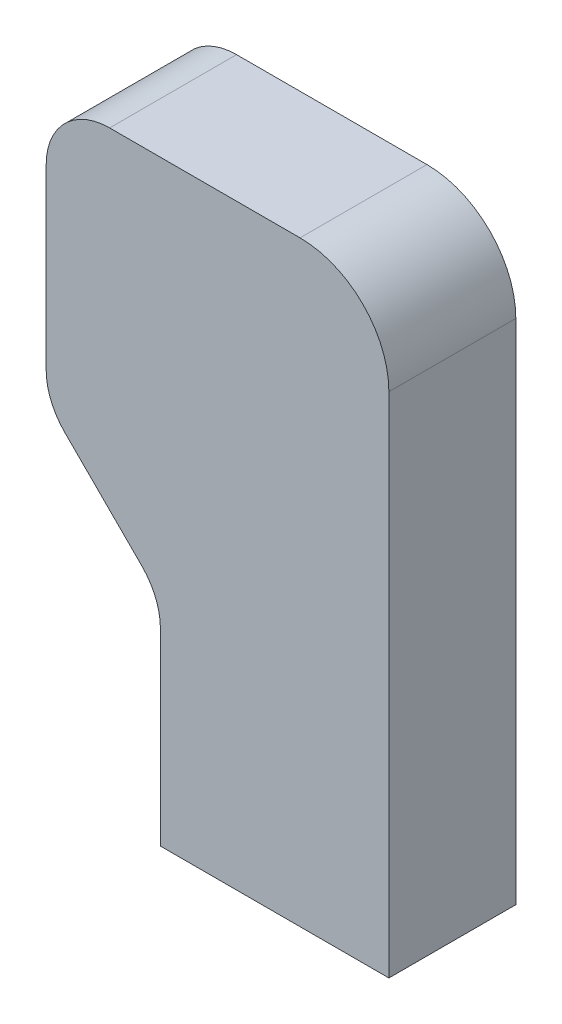
SolidWorks part; units mm, degrees
ref_plane "Front Plane" through (0, 0, 0) normal (0, 0, 1) x (1, 0, 0)
ref_plane "Top Plane" through (0, 0, 0) normal (0, 1, 0) x (1, 0, 0)
ref_plane "Right Plane" through (0, 0, 0) normal (1, 0, 0) x (0, 0, -1)
sketch "Sketch1" plane through (0, 0, 0) normal (0, 0, 1) x (1, 0, 0)
  line L0 (149.5414, 138.0219) -> (159.7945, 138.0219) construction
  line L12 (146.2984, 141.1279) -> (147.0694, 140.3568)
  line L13 (147.2554, 139.9078) -> (147.2554, 138.0219)
  line L14 (147.2554, 138.0219) -> (149.5414, 138.0219)
  line L15 (149.5414, 138.0219) -> (149.5414, 143.1019)
  line L16 (148.6524, 143.9909) -> (146.7474, 143.9909)
  line L17 (146.1124, 143.3559) -> (146.1124, 141.5769)
  arc A8 (146.1124, 141.5769) -> (146.2984, 141.1279) centre (146.7474, 141.5769) ccw
  arc A9 (147.2554, 139.9078) -> (147.0694, 140.3568) centre (146.6204, 139.9078) ccw
  arc A10 (149.5414, 143.1019) -> (148.6524, 143.9909) centre (148.6524, 143.1019) ccw
  arc A11 (146.7474, 143.9909) -> (146.1124, 143.3559) centre (146.7474, 143.3559) ccw
  dimension "D6" = 0.635
  dimension "D7" = 0.889
  dimension "D8" = 0.635
  dimension "D9" = 0.635
  dimension "D10" = 135
  dimension "D1" = 2.286
  dimension "D2" = 5.08
  dimension "D3" = 1.886
  dimension "D4" = 1.779
  dimension "D5" = 1.905
extrude "Boss-Extrude1" add sketch "Sketch1" along normal mid plane 1.27
sketch "Sketch2" plane through (0, 138.0219, 0) normal (0, -1, 0) x (1, 0, 0)
  line L16 (147.7634, -0.38) -> (149.0334, -0.38)
  line L17 (149.0334, -0.38) -> (149.0334, 0.38)
  line L18 (149.0334, 0.38) -> (147.7634, 0.38)
  line L19 (147.7634, 0.38) -> (147.7634, -0.38)
  point P0 (148.3984, 0)
  point P1 (148.3984, 0)
  point P3 (148.3984, 0)
extrude "Cut-Extrude1" cut sketch "Sketch2" against normal blind 4.74
fillet "Fillet1" 2 edges at (149.0334, 142.7619, 0) (147.7634, 142.7619, 0) type full round first side face at (149.0334, 140.3919, 0) second side face at (147.7634, 140.3919, 0) middle face at (148.3984, 142.7619, 0)
